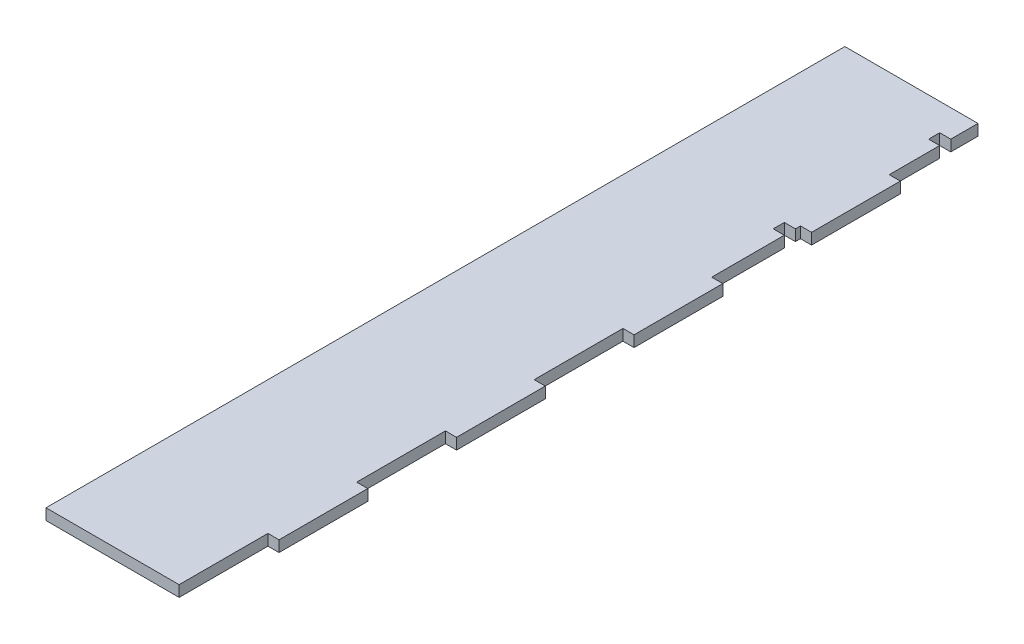
SolidWorks part; units mm, degrees
ref_plane "Front Plane" through (0, 0, 0) normal (0, 0, 1) x (1, 0, 0)
ref_plane "Top Plane" through (0, 0, 0) normal (0, 1, 0) x (1, 0, 0)
ref_plane "Right Plane" through (0, 0, 0) normal (1, 0, 0) x (0, 0, -1)
sketch "Sketch1" plane through (0, 0, 0) normal (0, 0, 1) x (1, 0, 0)
  line L1 (-38.1, -38.1) -> (38.1, -38.1) construction
  line L2 (-38.1, -38.1) -> (-38.1, 38.1) construction
  line L3 (-38.1, 38.1) -> (38.1, 38.1) construction
  line L4 (38.1, -38.1) -> (38.1, 38.1) construction
  line L5 (-38.1, -38.1) -> (38.1, 38.1) construction
  line L6 (-38.1, 38.1) -> (38.1, -38.1) construction
  line L7 (-38.1, -38.1) -> (38.1, -38.1)
  line L8 (-38.1, -38.1) -> (-38.1, -44.45)
  line L9 (-38.1, -44.45) -> (38.1, -44.45)
  line L10 (38.1, -38.1) -> (38.1, -44.45)
  point P0 (0, 0)
  dimension "D1" = 76.2
  dimension "D2" = 6.35
extrude "Boss-Extrude1" add sketch "Sketch1" along normal blind 457.2
sketch "Sketch2" plane through (38.1, 0, 0) normal (1, 0, 0) x (0, 0, -1)
  line L0 (-457.2, -44.45) -> (0, -44.45) construction
  line L1 (-406.4, -44.45) -> (-355.6, -44.45)
  line L2 (-406.4, -44.45) -> (-406.4, -38.1)
  line L3 (-406.4, -38.1) -> (-355.6, -38.1)
  line L4 (-355.6, -44.45) -> (-355.6, -38.1)
  line L5 (-406.4, -44.45) -> (-406.4, -38.1) construction
  line L6 (-355.6, -38.1) -> (-355.6, -44.45) construction
  line L7 (-457.2, -38.1) -> (0, -38.1) construction
  line L8 (-304.8, -44.45) -> (-304.8, -38.1) construction
  line L9 (-304.8, -44.45) -> (-254, -44.45)
  line L10 (-304.8, -44.45) -> (-304.8, -38.1)
  line L11 (-304.8, -38.1) -> (-254, -38.1)
  line L12 (-254, -44.45) -> (-254, -38.1)
  line L13 (-203.2, -44.45) -> (-152.4, -44.45)
  line L14 (-203.2, -44.45) -> (-203.2, -38.1)
  line L15 (-203.2, -38.1) -> (-152.4, -38.1)
  line L16 (-152.4, -44.45) -> (-152.4, -38.1)
  line L17 (-101.6, -44.45) -> (-50.8, -44.45)
  line L18 (-101.6, -44.45) -> (-101.6, -38.1)
  line L19 (-101.6, -38.1) -> (-50.8, -38.1)
  line L20 (-50.8, -44.45) -> (-50.8, -38.1)
  line L21 (-254, -38.1) -> (-254, -44.45) construction
  line L22 (-203.2, -44.45) -> (-203.2, -38.1) construction
  line L23 (-152.4, -38.1) -> (-152.4, -44.45) construction
  line L24 (-101.6, -44.45) -> (-101.6, -38.1) construction
  line L25 (-50.8, -38.1) -> (-50.8, -44.45) construction
extrude "Boss-Extrude2" add sketch "Sketch2" along normal up to surface (6.35 mm away) up to face at (38.1, -41.275, 228.6)
sketch "Sketch3" plane through (0, -38.1, 0) normal (0, 1, 0) x (1, 0, 0)
  line L0 (38.1, -152.4) -> (38.1, -101.6) construction
  line L1 (31.75, -104.4875) -> (38.1, -104.4875)
  line L2 (31.75, -104.4875) -> (31.75, -110.8375)
  line L3 (31.75, -110.8375) -> (38.1, -110.8375)
  line L4 (38.1, -104.4875) -> (38.1, -110.8375)
extrude "Cut-Extrude1" cut sketch "Sketch3" against normal blind 6.35
sketch "Sketch4" plane through (0, -38.1, 0) normal (0, 1, 0) x (1, 0, 0)
  line L0 (38.1, -50.8) -> (38.1, 0) construction
  line L1 (31.75, -21.9375) -> (38.1, -21.9375)
  line L2 (31.75, -21.9375) -> (31.75, -15.5875)
  line L3 (31.75, -15.5875) -> (38.1, -15.5875)
  line L4 (38.1, -21.9375) -> (38.1, -15.5875)
extrude "Cut-Extrude2" cut sketch "Sketch4" against normal through all
